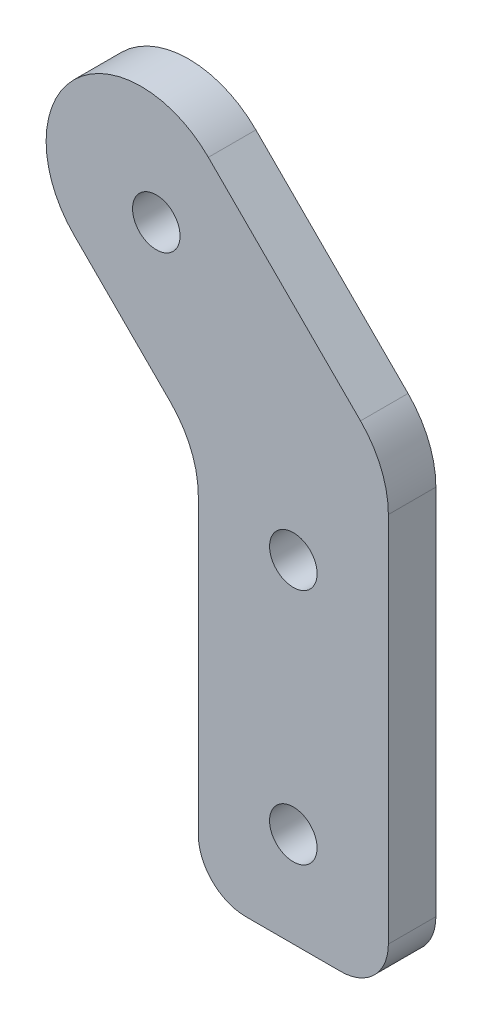
SolidWorks part; units mm, degrees
ref_plane "Front Plane" through (0, 0, 0) normal (0, 0, 1) x (1, 0, 0)
ref_plane "Top Plane" through (0, 0, 0) normal (0, 1, 0) x (1, 0, 0)
ref_plane "Right Plane" through (0, 0, 0) normal (1, 0, 0) x (0, 0, -1)
sketch "Sketch1" plane through (0, 0, 0) normal (0, 0, 1) x (1, 0, 0)
  line L0 (0, 0) -> (0, 40)
  line L1 (0, 40) -> (-20.1529, 60.1529)
  line L2 (-20.1529, 60.1529) -> (-6.0108, 74.2951)
  line L3 (-6.0108, 74.2951) -> (20, 48.2843)
  line L4 (20, 48.2843) -> (20, 0)
  line L5 (20, 0) -> (0, 0)
  line L6 (10, 74.2136) -> (10, -31.8756) construction
  line L7 (-23.6997, 77.8418) -> (34.4717, 19.6705) construction
  line L8 (0, 40) -> (20, 40) construction
  circle A0 centre (10, 10) radius 2.5
  circle A1 centre (10, 35) radius 2.5
  circle A2 centre (-4.4196, 58.5617) radius 9 construction
  circle A3 centre (-4.4196, 58.5617) radius 2.5
  point P9 (10, 0)
  point P16 (-13.0819, 67.224)
  dimension "D4" = 25
  dimension "D6" = 45
  dimension "D1" = 20
  dimension "D2" = 20
  dimension "D3" = 40
  dimension "D5" = 10
extrude "Boss-Extrude1" add sketch "Sketch1" along normal blind 5
fillet "Fillet1" radius 10 4 edges at (20, 48.2843, 2.5) (0, 40, 2.5) (-20.1529, 60.1529, 2.5) (-6.0108, 74.2951, 2.5)
fillet "Fillet2" radius 5 2 edges at (20, 0, 2.5) (0, 0, 2.5)
